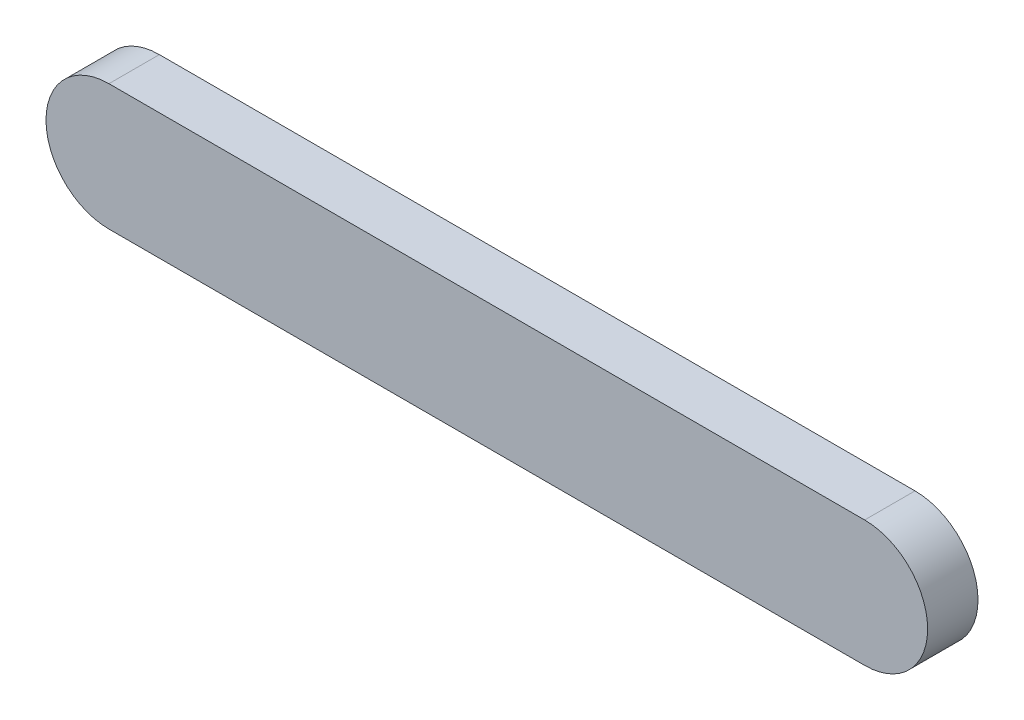
SolidWorks part; units mm, degrees
ref_plane "Front Plane" through (0, 0, 0) normal (0, 0, 1) x (1, 0, 0)
ref_plane "Top Plane" through (0, 0, 0) normal (0, 1, 0) x (1, 0, 0)
ref_plane "Right Plane" through (0, 0, 0) normal (1, 0, 0) x (0, 0, -1)
sketch "Sketch1" plane through (0, 0, 0) normal (0, 0, 1) x (1, 0, 0)
  line L0 (0, 0) -> (30, 0) construction
  line L1 (0, 2.5) -> (30, 2.5)
  line L2 (0, -2.5) -> (30, -2.5)
  arc A0 (0, 2.5) -> (0, -2.5) centre (0, 0) ccw
  arc A1 (30, -2.5) -> (30, 2.5) centre (30, 0) ccw
  point P3 (15, 0)
  dimension "D1" = 2.5
  dimension "D2" = 30
extrude "Boss-Extrude1" add sketch "Sketch1" along normal mid plane 2
